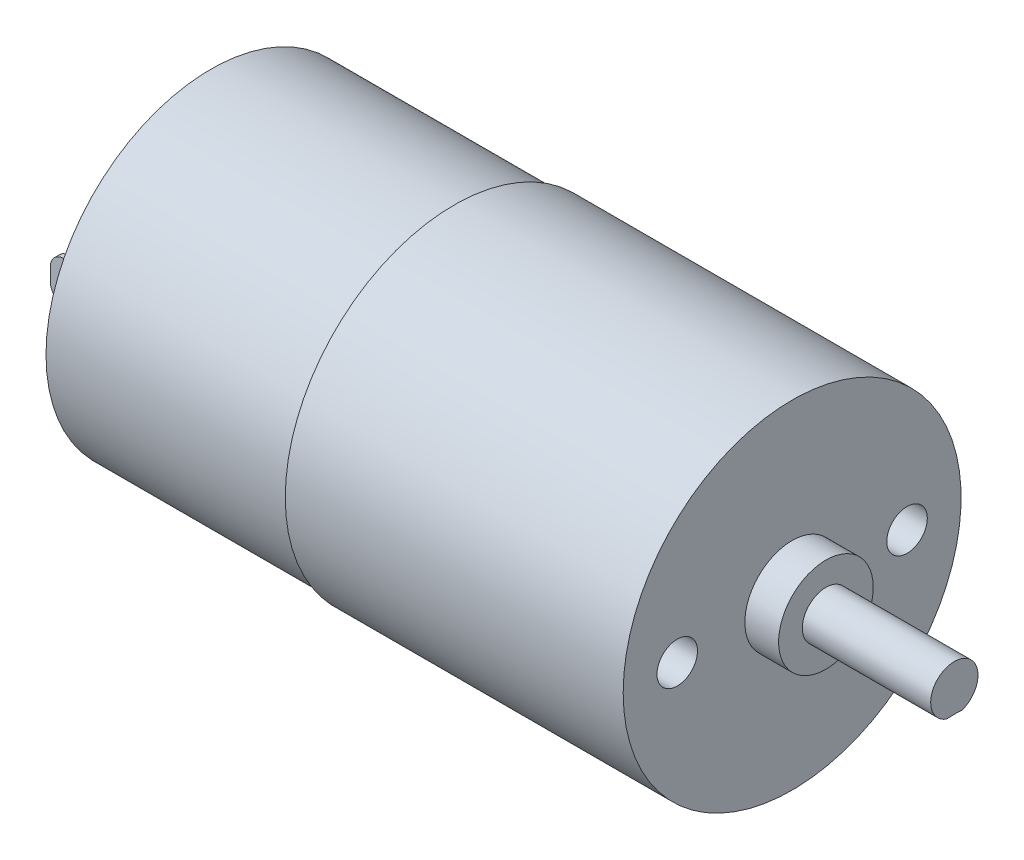
SolidWorks part; units mm, degrees
ref_plane "Front Plane" through (0, 0, 0) normal (0, 0, 1) x (1, 0, 0)
ref_plane "Top Plane" through (0, 0, 0) normal (0, 1, 0) x (1, 0, 0)
ref_plane "Right Plane" through (0, 0, 0) normal (1, 0, 0) x (0, 0, -1)
ref_plane "Plano1" through (0, 0, 0) normal (0, 0, -1) x (-1, 0, 0)
sketch "Croquis1" plane through (0, 0, 0) normal (0, 0, -1) x (-1, 0, 0)
  line L0 (1.5, 18.4) -> (1.5, 5.9)
  line L1 (1.5, 5.9) -> (26.5, 5.9)
  line L2 (26.5, 5.9) -> (26.5, 18.4)
  line L3 (26.5, 18.4) -> (1.5, 18.4)
  line L4 (1.5, 5.9) -> (26.5, 5.9) construction
  dimension "D1" = 12.5
  dimension "D2" = 25
revolve "Revolución1" add sketch "Croquis1" angle 360 about L4 reverse direction yes
sketch "Croquis2" plane through (-1.5, 0, 0) normal (1, 0, 0) x (0, 0, -1)
  circle A0 centre (0, 5.9) radius 3.5
  circle A1 centre (0, 5.9) radius 12.5 construction
  dimension "D2" = 7
  dimension "D1" = 0
extrude "Saliente-Extruir1" add sketch "Croquis2" along normal blind 2.5
sketch "Croquis3" plane through (1, 0, 0) normal (1, 0, 0) x (0, 0, -1)
  circle A0 centre (0, 5.9) radius 1.75
  circle A5 centre (0, 5.9) radius 3.5 construction
  dimension "D1" = 3.5
extrude "Saliente-Extruir2" add sketch "Croquis3" along normal blind 9.5
sketch "Croquis4" plane through (10.5, 0, 0) normal (1, 0, 0) x (0, 0, -1)
  line L0 (-1.4967, 4.15) -> (1.4967, 4.15)
  arc A0 (1.4967, 4.15) -> (-1.4967, 4.15) centre (0, -5.6) ccw
  circle A3 centre (0, 5.9) radius 1.75 construction
  point P3 (0, 4.15)
extrude "Cortar-Extruir1" cut sketch "Croquis4" against normal blind 8
sketch "Croquis5" plane through (-26.5, 0, 0) normal (-1, 0, 0) x (0, 0, 1)
  circle A0 centre (0, 5.9) radius 12.2
  circle A1 centre (0, 5.9) radius 12.5 construction
  dimension "D1" = 24.4
extrude "Saliente-Extruir3" add sketch "Croquis5" along normal blind 18
hole_wizard "Diámetro de taladro Ø3.0 (3)1" positions "Croquis9" profile "Croquis8" hole size "Ø3.0" standard "Ansi Metric"
sketch "Croquis9" plane through (-1.5, 0, 0) normal (1, 0, 0) x (0, 0, -1)
  line L0 (-2.5616, 5.8271) -> (-50002.5616, 5.8271) construction
  circle A13 centre (0, 5.9) radius 12.5 construction
  point P1 (-8.5, 5.8271)
  point P3 (8.5, 5.8271)
  dimension "D1" = 17
  dimension "D2" = 8.5
sketch "Croquis8" plane through (-1.5, 5.8271, 8.5) normal (0, 1, 0) x (0, 0, -1)
  line L0 (0, 0) -> (0, 8)
  line L1 (0, 8) -> (1.5, 8)
  line L2 (1.5, 8) -> (1.5, 0)
  line L5 (1.5, 0) -> (0, 0)
  line L10 (0, 8) -> (-1.5, 8) construction
  line L11 (0, -6.35) -> (0, 107.95) construction
  dimension "Diámetro de taladro" = 3
  dimension "Profundidad de taladro" = 8
  dimension "Ángulo de perforador" = 180
sketch "Croquis10" plane through (-44.5, 0, 0) normal (-1, 0, 0) x (0, 0, 1)
  circle A0 centre (0, 5.9) radius 11.5
  dimension "D1" = 23
extrude "Cortar-Extruir2" cut sketch "Croquis10" against normal blind 2
sketch "Croquis11" plane through (-42.5, 0, 0) normal (-1, 0, 0) x (0, 0, 1)
  line L0 (0.0284, 19.0333) -> (0.0284, 50019.0333) construction
  line L1 (0, 5.9) -> (-50000, 5.9) construction
  line L3 (-5.135, 3.4) -> (-6.135, 3.4)
  line L4 (-4.635, 3.9) -> (-4.635, 7.9)
  line L5 (-5.135, 8.4) -> (-6.135, 8.4)
  line L6 (-6.635, 3.9) -> (-6.635, 7.9)
  line L7 (-4.635, 3.4) -> (-6.635, 8.4) construction
  line L8 (-4.635, 8.4) -> (-6.635, 3.4) construction
  line L9 (7.125, 3.4) -> (6.125, 3.4)
  line L10 (7.625, 3.9) -> (7.625, 7.9)
  line L11 (7.125, 8.4) -> (6.125, 8.4)
  line L12 (5.625, 3.9) -> (5.625, 7.9)
  line L13 (7.625, 3.4) -> (5.625, 8.4) construction
  line L14 (7.625, 8.4) -> (5.625, 3.4) construction
  arc A0 (6.125, 3.4) -> (5.625, 3.9) centre (6.125, 3.9) cw
  arc A1 (7.125, 3.4) -> (7.625, 3.9) centre (7.125, 3.9) ccw
  arc A2 (7.625, 7.9) -> (7.125, 8.4) centre (7.125, 7.9) ccw
  arc A3 (6.125, 8.4) -> (5.625, 7.9) centre (6.125, 7.9) ccw
  arc A4 (-5.135, 3.4) -> (-4.635, 3.9) centre (-5.135, 3.9) ccw
  arc A5 (-6.135, 3.4) -> (-6.635, 3.9) centre (-6.135, 3.9) cw
  arc A6 (-6.135, 8.4) -> (-6.635, 7.9) centre (-6.135, 7.9) ccw
  arc A7 (-4.635, 7.9) -> (-5.135, 8.4) centre (-5.135, 7.9) ccw
  point P4 (-5.635, 5.9)
  point P10 (6.625, 5.9)
  dimension "D5" = 0.5
  dimension "D1" = 10.26
  dimension "D2" = 5.5965
  dimension "D3" = 2
  dimension "D4" = 5
extrude "Saliente-Extruir4" add sketch "Croquis11" along normal blind 1
sketch "Croquis12" plane through (-43.5, 0, 0) normal (-1, 0, 0) x (0, 0, 1)
  line L0 (7.625, 3.9) -> (7.625, 7.9) construction
  line L1 (-5.4376, 4.3377) -> (-5.8376, 4.3377)
  line L2 (-5.4376, 4.3377) -> (-5.4376, 7.3377)
  line L3 (-5.4376, 7.3377) -> (-5.8376, 7.3377)
  line L4 (-5.8376, 4.3377) -> (-5.8376, 7.3377)
  line L5 (-5.4376, 4.3377) -> (-5.8376, 7.3377) construction
  line L6 (-5.4376, 7.3377) -> (-5.8376, 4.3377) construction
  line L7 (6.8777, 4.4) -> (6.4777, 4.4)
  line L8 (6.8777, 4.4) -> (6.8777, 7.4)
  line L9 (6.8777, 7.4) -> (6.4777, 7.4)
  line L10 (6.4777, 4.4) -> (6.4777, 7.4)
  line L11 (6.8777, 4.4) -> (6.4777, 7.4) construction
  line L12 (6.8777, 7.4) -> (6.4777, 4.4) construction
  point P0 (-5.6376, 5.8377)
  point P5 (6.6777, 5.9)
  point P13 (7.625, 5.9)
  dimension "D1" = 0.4
  dimension "D2" = 3
  dimension "D3" = 0.4
  dimension "D4" = 3
extrude "Saliente-Extruir5" add sketch "Croquis12" along normal blind 6
fillet "Redondeo1" radius 1 4 edges at (-49.5, 4.4, 6.6777) (-49.5, 7.4, 6.6777) (-49.5, 4.3377, -5.6376) (-49.5, 7.3377, -5.6376)
sketch "Croquis14" plane through (0, 0, 6.8777) normal (0, 0, 1) x (1, 0, 0)
  line L0 (-49.5, 5.4) -> (-49.5, 6.4) construction
  line L1 (-45.3, 5.2) -> (-47.7, 5.2)
  line L2 (-45, 5.5) -> (-45, 6.3)
  line L3 (-45.3, 6.6) -> (-47.7, 6.6)
  line L4 (-48, 5.5) -> (-48, 6.3)
  line L5 (-45, 5.2) -> (-48, 6.6) construction
  line L6 (-45, 6.6) -> (-48, 5.2) construction
  arc A0 (-45, 6.3) -> (-45.3, 6.6) centre (-45.3, 6.3) ccw
  arc A1 (-45.3, 5.2) -> (-45, 5.5) centre (-45.3, 5.5) ccw
  arc A2 (-47.7, 5.2) -> (-48, 5.5) centre (-47.7, 5.5) cw
  arc A3 (-47.7, 6.6) -> (-48, 6.3) centre (-47.7, 6.3) ccw
  point P0 (-46.5, 5.9)
  point P5 (-48, 5.9)
  point P8 (-49.5, 5.9)
  dimension "D4" = 0.3
  dimension "D1" = 3
  dimension "D2" = 1.5
  dimension "D3" = 1.4
extrude "Cortar-Extruir3" cut sketch "Croquis14" against normal through all
sketch "Croquis15" plane through (-42.5, 0, 0) normal (-1, 0, 0) x (0, 0, 1)
  line L0 (0, 17.4) -> (0, 50017.4) construction
  circle A2 centre (0, 5.9) radius 2.5
  dimension "D1" = 5
extrude "Saliente-Extruir6" add sketch "Croquis15" along normal blind 2
sketch "Croquis16" plane through (-42.5, 0, 0) normal (-1, 0, 0) x (0, 0, 1)
  circle A0 centre (0, 5.9) radius 1.5
  dimension "D1" = 3
extrude "Saliente-Extruir7" add sketch "Croquis16" along normal blind 3
chamfer "Chaflán1" distance 1 angle 20 1 edges at (-45.5, 5.9, 1.5) first distance on face at (-44.5, 5.9, 1.5)
sketch "Croquis17" plane through (-45.5, 0, 0) normal (-1, 0, 0) x (0, 0, 1)
  circle A0 centre (0, 5.9) radius 1
  dimension "D1" = 2
extrude "Cortar-Extruir4" cut sketch "Croquis17" against normal blind 1
